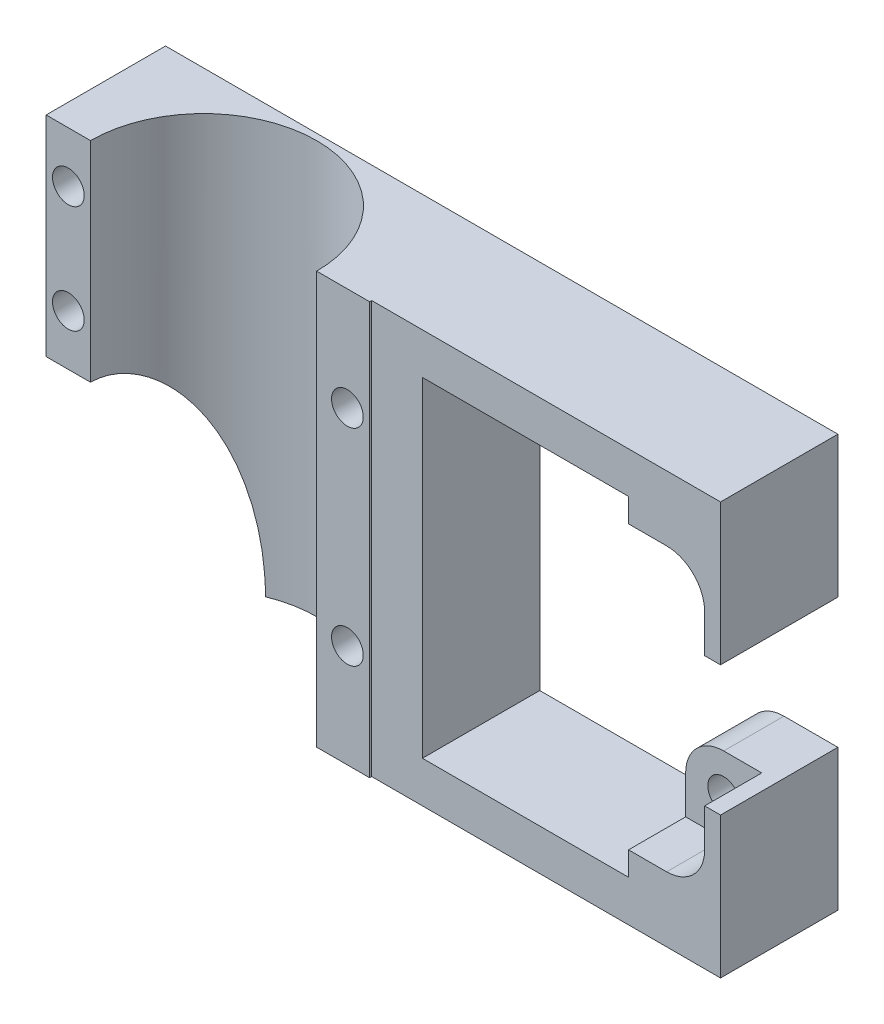
SolidWorks part; units mm, degrees
ref_plane "Front Plane" through (0, 0, 0) normal (0, 0, 1) x (1, 0, 0)
ref_plane "Top Plane" through (0, 0, 0) normal (0, 1, 0) x (1, 0, 0)
ref_plane "Right Plane" through (0, 0, 0) normal (1, 0, 0) x (0, 0, -1)
sketch "Sketch1" plane through (0, 0, 0) normal (0, 0, 1) x (1, 0, 0)
  line L0 (147, 32.5) -> (55.5, 32.5)
  line L1 (161.5, 32.5) -> (161.5, 10.25)
  line L3 (161.5, -32.5) -> (147, -32.5)
  line L4 (147, -32.5) -> (73.58, -32.5)
  line L5 (73.58, -32.5) -> (21.8306, -32.5) construction
  line L6 (62.5, -0.5) -> (55.5, -0.5)
  line L7 (55.5, -0.5) -> (55.5, 32.5)
  line L8 (59, -0.5) -> (59, 32.5) construction
  line L9 (161.5, 32.5) -> (97, 32.5) construction
  line L10 (99.5, -32.5) -> (99.5, 32.5)
  line L11 (106.5, 32.5) -> (106.5, -32.5)
  line L12 (62.5, -0.5) -> (62.5, 32.5)
  line L13 (147, 32.5) -> (147, 16.25) construction
  line L14 (161.5, -32.5) -> (97, -32.5) construction
  line L15 (147, -16.25) -> (147, -26)
  line L16 (147, -26) -> (114.5, -26)
  line L18 (114.5, 26) -> (114.5, -26)
  line L20 (161.5, 0) -> (121.6216, 0) construction
  line L21 (161.5, -32.5) -> (161.5, 32.5) construction
  line L22 (161.5, 32.5) -> (147, 32.5)
  line L23 (147, 16.25) -> (147, 26)
  line L25 (147, 26) -> (114.5, 26)
  line L26 (153, -10.25) -> (161.5, -10.25)
  line L27 (153, 10.25) -> (161.5, 10.25)
  line L28 (147, -16.25) -> (147, -32.5) construction
  line L29 (161.5, -10.25) -> (161.5, -32.5)
  arc A0 (73.58, -32.5) -> (62.5, -0.5) centre (21.8306, -32.5) ccw
  circle A1 centre (59, 7.5) radius 2.5
  circle A2 centre (59, 24.5) radius 2.5
  circle A3 centre (103, 16.25) radius 2.5 construction
  circle A4 centre (153, 16.25) radius 2.5 construction
  circle A7 centre (103, -16.25) radius 2.5
  circle A8 centre (103, 16.25) radius 2.5
  circle A9 centre (153, -16.25) radius 2.5
  circle A10 centre (153, 16.25) radius 2.5
  arc A11 (147, 16.25) -> (153, 10.25) centre (153, 16.25) ccw
  arc A12 (147, -16.25) -> (153, -10.25) centre (153, -16.25) cw
  point P49 (114.5, 0)
  dimension "D4" = 5
  dimension "D5" = 5
  dimension "D7" = 3.5
  dimension "D8" = 3.5
  dimension "D11" = 6
  dimension "D14" = 6
  dimension "D16" = 5
  dimension "D17" = 5
  dimension "D15" = 5
  dimension "D18" = 5
  dimension "D19" = 6
  dimension "D1" = 18.08
  dimension "D2" = 7
  dimension "D3" = 33
  dimension "D6" = 17
  dimension "D9" = 51
  dimension "D10" = 8
  dimension "D12" = 52
  dimension "D13" = 32.5
extrude "Boss-Extrude3" add sketch "Sketch1" along normal blind 18.5 contours L1 L22 L0 L11 L4 L3 A10 A9 L25 L23 L15 L16 L18 region at (154.25, 31.6485, 0)
sketch "Sketch2" plane through (0, 0, 18.5) normal (0, 0, 1) x (1, 0, 0)
  line L0 (153, 22.25) -> (147, 22.25)
  line L1 (147, 16.25) -> (147, 26) construction
  line L2 (159, 16.25) -> (159, 10.25)
  line L3 (153, 10.25) -> (161.5, 10.25) construction
  line L7 (153, -22.25) -> (147, -22.25)
  line L8 (147, -16.25) -> (147, -26) construction
  line L9 (159, 10.25) -> (147, 10.25)
  line L10 (147, 10.25) -> (147, 22.25)
  line L11 (147, -22.25) -> (147, -10.25)
  line L12 (147, -10.25) -> (159, -10.25)
  line L13 (159, -16.25) -> (159, -10.25)
  arc A0 (153, -22.25) -> (159, -16.25) centre (153, -16.25) ccw
  arc A1 (159, 16.25) -> (153, 22.25) centre (153, 16.25) ccw
  arc A2 (153, -10.25) -> (147, -16.25) centre (153, -16.25) ccw construction
  dimension "D1" = 12
  dimension "D2" = 12
extrude "Cut-Extrude2" cut sketch "Sketch2" against normal blind 9
extrude "Boss-Extrude4" add sketch "Sketch1<5>" along normal blind 18.825 contours A0 L4 L10 L0 L12 | L6 L12 L0 L7 A2 A1 | L11 L0 L10 L4 A8 A7 region at (103, 0, 0) region at (82.5687, 2.2715, 0) region at (59, 16, 0)
sketch "Sketch1<5>" plane through (0, 0, 0) normal (0, 0, 1) x (1, 0, 0) same geometry as "Sketch1"
sketch "Sketch3" plane through (0, -32.5, 0) normal (0, -1, 0) x (1, 0, 0)
  line L0 (45.7398, 18.825) -> (151.0188, 18.825) construction
  line L1 (106.5, 18.825) -> (73.58, 18.825) construction
  line L2 (62.5, 18.825) -> (62.5, 0) construction
  circle A0 centre (80.325, 18.825) radius 17.825
  point P6 (0, 0)
  dimension "D1" = 35.65
  dimension "D2" = 17.825
extrude "Cut-Extrude3" cut sketch "Sketch3" against normal through all
